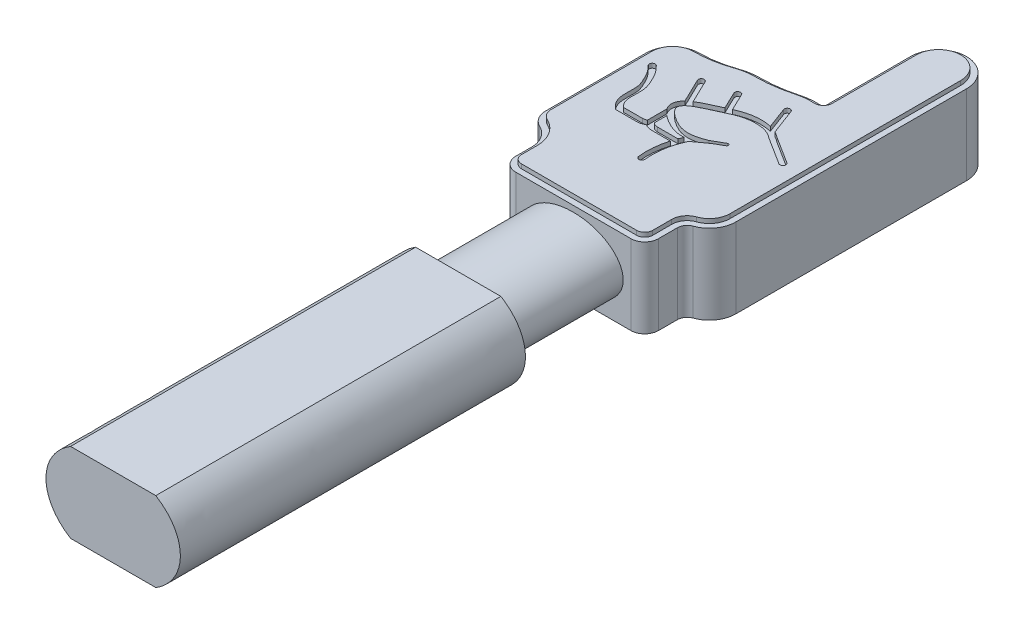
SolidWorks part; units mm, degrees
ref_plane "Plan de face" through (0, 0, 0) normal (0, 0, 1) x (1, 0, 0)
ref_plane "Plan de dessus" through (0, 0, 0) normal (0, 1, 0) x (1, 0, 0)
ref_plane "Plan de droite" through (0, 0, 0) normal (1, 0, 0) x (0, 0, -1)
sketch "Esquisse2" plane through (0, 0, 0) normal (0, 1, 0) x (1, 0, 0)
  line L4 (-461.3514, 50.6784) -> (-461.3514, 90.7755)
  line L5 (-471.0713, 90.7755) -> (-471.0713, 76.1755)
  line L6 (-465.5648, 44.7364) -> (-465.5648, 41.4326)
  line L7 (-467.9625, 39.035) -> (-487.9825, 39.035)
  line L8 (-490.3801, 41.4326) -> (-490.3801, 44.1985)
  line L9 (-494.5966, 50.8393) -> (-494.5966, 68.3008)
  arc A17 (-461.3514, 90.7755) -> (-471.0713, 90.7755) centre (-466.2114, 90.7755) ccw
  arc A18 (-471.0713, 76.1755) -> (-471.6659, 75.6215) centre (-471.6268, 76.1755) cw
  arc A19 (-471.6659, 75.6215) -> (-474.8438, 75.3021) centre (-472.3289, 66.2484) ccw
  arc A20 (-461.3514, 50.6784) -> (-464.4333, 46.3321) centre (-465.9571, 50.6784) cw
  arc A21 (-464.4333, 46.3321) -> (-465.5648, 44.7364) centre (-463.8739, 44.7364) ccw
  arc A22 (-465.5648, 41.4326) -> (-467.9625, 39.035) centre (-467.9625, 41.4326) cw
  arc A23 (-487.9825, 39.035) -> (-490.3801, 41.4326) centre (-487.9825, 41.4326) cw
  arc A24 (-490.3801, 44.1985) -> (-492.803, 48.0144) centre (-494.5966, 44.1985) ccw
  arc A25 (-492.803, 48.0144) -> (-494.5966, 50.8393) centre (-491.4751, 50.8393) cw
  arc A26 (-494.5966, 68.3008) -> (-489.9856, 72.9117) centre (-489.9856, 68.3008) cw
  arc A27 (-489.9856, 72.9117) -> (-484.1893, 73.9115) centre (-489.9856, 90.214) ccw
  arc A28 (-484.1893, 73.9115) -> (-480.9635, 74.4679) centre (-480.9635, 64.8387) cw
  arc A29 (-480.9635, 74.4679) -> (-474.8438, 75.3021) centre (-480.9635, 97.3326) ccw
  dimension "D3" = 14.6
  dimension "D4" = 0.5554
  dimension "D5" = 9.3965
  dimension "D6" = 4.6057
  dimension "D7" = 1.6909
  dimension "D8" = 2.3977
  dimension "D9" = 4.2164
  dimension "D10" = 3.1214
  dimension "D11" = 4.6109
  dimension "D12" = 17.3023
  dimension "D13" = 9.6292
  dimension "D1" = 9.72
  dimension "D2" = 461.3514
  dimension "D15" = 472.3289
  dimension "D16" = 465.5648
  dimension "D17" = 480.9635
  dimension "D18" = 484.1893
  dimension "D19" = 72.9117
  dimension "D21" = 50.8393
  dimension "D22" = 50.6784
  dimension "D36" = 39.035
extrude "Boss.-Extru.1" add sketch "Esquisse2" along normal blind 14.6
sketch "Esquisse4" plane through (0, 14.6, 0) normal (0, 1, 0) x (1, 0, 0)
  line L0 (-472.4313, 71.3413) -> (-470.759, 66.8763)
  line L1 (-479.2673, 69.577) -> (-477.8287, 66.5691)
  line L2 (-484.8272, 68.1421) -> (-483.1754, 64.6884)
  line L3 (-487.6052, 57.4055) -> (-484.2817, 57.4055)
  line L5 (-478.1514, 57.4055) -> (-481.7388, 57.4055)
  line L6 (-490.4583, 65.8897) -> (-491.0481, 66.5366)
  line L7 (-491.0481, 66.5366) -> (-472.4313, 71.3413) construction
  line L8 (-461.3514, 50.6784) -> (-461.3514, 90.7755) construction
  line L9 (-473.3677, 70.9906) -> (-471.9932, 67.3203)
  line L10 (-480.1694, 69.1456) -> (-478.7397, 66.1562)
  line L12 (-491.1972, 65.2159) -> (-491.787, 65.8628)
  line L13 (-487.9601, 56.4055) -> (-484.2783, 56.4055)
  line L14 (-477.4426, 56.4055) -> (-481.7388, 56.4055)
  line L16 (-483.1205, 57.4055) -> (-483.1205, 61.028) construction
  line L17 (-483.6205, 57.5979) -> (-483.6205, 60.9564)
  line L18 (-484.8272, 68.1421) -> (-482.7323, 63.7919) construction
  line L19 (-484.3767, 68.359) -> (-482.4341, 64.3251)
  line L20 (-485.2777, 67.9251) -> (-483.2443, 63.7026)
  line L21 (-470.3753, 65.4409) -> (-465.3514, 62.8537) construction
  line L22 (-469.8136, 66.2662) -> (-465.0842, 63.2763)
  line L23 (-470.348, 65.421) -> (-465.6185, 62.4311)
  line L24 (-473.0349, 60.7918) -> (-475.4776, 59.3877) construction
  line L25 (-472.8992, 60.5556) -> (-474.5084, 59.6306)
  line L26 (-473.1707, 61.028) -> (-475.2006, 59.8612)
  line L27 (-482.6205, 57.7552) -> (-482.6205, 59.9234)
  arc A0 (-484.2817, 57.4055) -> (-483.6205, 57.5979) centre (-484.2916, 58.6719) ccw
  arc A1 (-476.8297, 57.9491) -> (-477.9359, 51.4698) centre (-466.0442, 52.7736) ccw
  arc A3 (-481.7388, 57.4055) -> (-482.6205, 57.7552) centre (-481.7388, 58.692) cw
  arc A5 (-484.2783, 56.4055) -> (-483.0183, 56.797) centre (-484.2916, 58.6719) ccw
  arc A6 (-481.7388, 56.4055) -> (-483.0183, 56.797) centre (-481.7388, 58.692) cw
  arc A7 (-477.8343, 58.1619) -> (-478.1514, 57.4055) centre (-466.0442, 52.7736) ccw
  arc A8 (-472.4313, 71.3413) -> (-473.3677, 70.9906) centre (-472.8995, 71.1659) ccw
  arc A10 (-479.2673, 69.577) -> (-480.1694, 69.1456) centre (-479.7183, 69.3613) ccw
  arc A14 (-491.0481, 66.5366) -> (-491.787, 65.8628) centre (-491.4176, 66.1997) ccw
  arc A18 (-470.4025, 65.4609) -> (-470.348, 65.421) centre (-470.3753, 65.4409) ccw
  arc A19 (-477.9359, 51.4698) -> (-478.93, 51.3609) centre (-478.433, 51.4154) cw
  arc A21 (-484.3767, 68.359) -> (-485.2777, 67.9251) centre (-484.8272, 68.1421) ccw
  arc A23 (-470.4025, 65.4609) -> (-470.348, 65.421) centre (-470.3753, 65.4409) ccw
  arc A24 (-465.6185, 62.4311) -> (-465.0842, 63.2763) centre (-465.3514, 62.8537) ccw
  arc A25 (-472.8992, 60.5556) -> (-473.1707, 61.028) centre (-473.0349, 60.7918) ccw
  arc A27 (-478.488, 56.4055) -> (-478.93, 51.3609) centre (-466.0442, 52.7736) ccw
  spline S0 degree 3 poles (-490.4583, 65.8897) (-489.9643, 65.3478) (-489.2576, 64.0084) (-488.0431, 61.1753) (-489.0579, 58.5852) (-487.6052, 57.4055) knots 0 0 0 0 0.249547 0.474449 1 1 1 1
  spline S1 degree 3 poles (-483.1823, 64.7264) (-483.18, 64.7137) (-483.1777, 64.7011) (-483.1754, 64.6884) knots 0.246141 0.246141 0.246141 0.246141 0.248714 0.248714 0.248714 0.248714
  spline S2 degree 3 poles (-470.4025, 65.4609) (-471.657, 66.5152) (-475.3225, 66.8063) (-478.8719, 64.9069) (-484.364, 62.5575) (-480.7126, 59.6038) (-478.2259, 58.8088) (-475.901, 59.5831) (-475.2006, 59.8612) knots 0 0 0 0 0.163612 0.32751 0.477242 0.563601 0.697734 0.765481 0.765481 0.765481 0.765481
  spline S3 degree 2 poles (-474.5084, 59.6306) (-475.3996, 58.9745) (-476.8297, 57.9491) knots 0.955294 0.955294 0.955294 1 1 1
  spline S4 degree 3 poles (-483.2443, 63.7026) (-483.4189, 63.536) (-483.7603, 63.1422) (-484.042, 62.4144) (-483.9809, 61.7052) (-483.8197, 61.2849) (-483.6856, 61.0541) (-483.6205, 60.9564) knots 0.428302 0.428302 0.428302 0.428302 0.447364 0.468667 0.479319 0.48997 0.498689 0.498689 0.498689 0.498689
  spline S5 degree 3 poles (-478.7397, 66.1562) (-478.841, 66.109) (-479.3545, 65.8687) (-480.3361, 65.4112) (-481.5724, 64.8367) (-482.2436, 64.4471) (-482.4341, 64.3251) knots 0.287644 0.287644 0.287644 0.287644 0.298243 0.340849 0.383455 0.401257 0.401257 0.401257 0.401257
  spline S6 degree 3 poles (-491.1972, 65.2159) (-491.0951, 65.1039) (-490.914, 64.8749) (-490.5473, 64.3017) (-490.1129, 63.4322) (-489.672, 62.4162) (-489.5049, 61.5865) (-489.5458, 60.4567) (-489.5779, 59.3459) (-489.4093, 58.37) (-489.1649, 57.7435) (-488.8551, 57.2619) (-488.58, 56.9296) (-488.2037, 56.5974) (-488.0493, 56.478) (-487.9601, 56.4055) knots 0 0 0 0 0.064576 0.129153 0.258306 0.387458 0.516611 0.645764 0.774917 0.839493 0.90407 0.936358 0.968646 1.000934 1.033223 1.033223 1.033223 1.033223
  spline S7 degree 3 poles (-471.9932, 67.3203) (-472.1805, 67.365) (-473.344, 67.5872) (-475.4797, 67.4725) (-477.0435, 66.9088) (-477.8287, 66.5691) knots 0.068798 0.068798 0.068798 0.068798 0.085212 0.170424 0.255222 0.255222 0.255222 0.255222
  spline S8 degree 3 poles (-469.7591, 66.2264) (-470.0622, 66.4812) (-470.4037, 66.6993) (-470.759, 66.8763) knots 0 0 0 0 0.03228 0.03228 0.03228 0.03228
  spline S9 degree 3 poles (-482.6205, 59.9234) (-482.4376, 59.7779) (-481.8068, 59.3219) (-480.7516, 58.706) (-479.3663, 58.2092) (-478.3366, 58.1325) (-477.8343, 58.1619) knots 0.535686 0.535686 0.535686 0.535686 0.553879 0.596485 0.639091 0.681698 0.681698 0.681698 0.681698
  point P38 (-483.7797, 65.967)
  point P58 (-483.1205, 59.2167)
  point P61 (-474.2563, 60.0898)
  point P67 (-467.7161, 64.3487)
  dimension "D4" = 1.2865
  dimension "D6" = 4.6928
  dimension "D9" = 2.2865
  dimension "D10" = 11.0799
  dimension "D11" = 11.1625
  dimension "D13" = 13.661
  dimension "D1" = 1.2664
  dimension "D2" = 11.963
  dimension "D5" = 0.5
  dimension "D7" = 2.2664
  dimension "D12" = 0.0338
  dimension "D15" = 0.2724
  dimension "D8" = 1
  dimension "D14" = 15.4783
  dimension "D16" = 16.0443
  dimension "D17" = 3.7328
  dimension "D18" = 16.5846
  dimension "D19" = 17.9159
  dimension "D20" = 18.1649
  dimension "D21" = 1
  dimension "D22" = 20.3874
  dimension "D23" = 21.6423
  dimension "D24" = 4
  dimension "D25" = 21.824
  dimension "D26" = 5.1377
  dimension "D27" = 4.2671
  dimension "D28" = 23.4758
  dimension "D29" = 26.2538
  dimension "D30" = 27.0797
  dimension "D31" = 27.2299
  dimension "D32" = 27.9056
  dimension "D33" = 29.1069
  dimension "D34" = 29.6967
  dimension "D35" = 12.8812
  dimension "D36" = 13.8294
  dimension "D37" = 6.3647
  dimension "D38" = 8.4077
  dimension "D39" = 17.6054
  dimension "D40" = 18.3562
  dimension "D41" = 8.4623
  dimension "D42" = 9.0239
  dimension "D43" = 19.5575
  dimension "D44" = 11.5481
  dimension "D45" = 16.0912
  dimension "D46" = 9.4077
  dimension "D47" = 10.6418
  dimension "D48" = 11.5478
  dimension "D49" = 18.3669
  dimension "D50" = 11.6836
  dimension "D51" = 11.8193
  dimension "D52" = 21.2691
  dimension "D53" = 12.9049
  dimension "D54" = 13.157
  dimension "D55" = 13.8492
  dimension "D56" = 21.6669
  dimension "D57" = 16.4773
  dimension "D58" = 16.4829
  dimension "D59" = 23.0253
  dimension "D60" = 30.0662
  dimension "D61" = 12.8846
  dimension "D62" = 17.3883
  dimension "D63" = 16.099
  dimension "D64" = 12.3497
  dimension "D65" = 18.3943
  dimension "D66" = 19.8742
  dimension "D67" = 21.0827
  dimension "D70" = 21.7691
  dimension "D71" = 21.8309
  dimension "D72" = 21.8929
  dimension "D73" = 13.5913
  dimension "D74" = 22.4283
  dimension "D75" = 13.7576
  dimension "D79" = 15.6533
  dimension "D80" = 26.6087
  dimension "D84" = 18.0165
  dimension "D90" = 19.8943
  dimension "D92" = 20.076
extrude "Cut-Extrude1" cut sketch "Esquisse4" against normal blind 0.75 contours S8 L0 A8 L9 S7 L1 A10 L10 S5 L19 A21 L20 S4 L17 A0 L3 S0 L6 A14 L12 S6 L13 A5 A6 L14 A1 S3 L25 A25 L26 S2 A18 L23 A24 L22 L27 S9 A7 L5 A3 | L14 A27 A19 A1 region at (-471.8861, 14.6, -68.9998) region at (-478.3729, 14.6, -53.7296)
sketch "Sketch1" plane through (0, 14.6, 0) normal (0, 1, 0) x (1, 0, 0)
  line L0 (-462.3514, 50.6784) -> (-462.3514, 90.7755)
  line L1 (-470.0713, 90.7755) -> (-470.0713, 76.1755)
  line L2 (-493.5966, 68.3008) -> (-493.5966, 50.8393)
  line L3 (-489.3801, 44.1985) -> (-489.3801, 41.4326)
  line L4 (-487.9825, 40.035) -> (-467.9625, 40.035)
  line L5 (-466.5648, 41.4326) -> (-466.5648, 44.7364)
  line L6 (-461.3514, 50.6784) -> (-461.3514, 90.7755)
  line L7 (-471.0713, 90.7755) -> (-471.0713, 76.1755)
  line L8 (-494.5966, 68.3008) -> (-494.5966, 50.8393)
  line L9 (-490.3801, 44.1985) -> (-490.3801, 41.4326)
  line L10 (-487.9825, 39.035) -> (-467.9625, 39.035)
  line L11 (-465.5648, 41.4326) -> (-465.5648, 44.7364)
  line L12 (-461.3514, 50.6784) -> (-461.3514, 90.7755)
  line L13 (-471.0713, 90.7755) -> (-471.0713, 76.1755)
  line L14 (-494.5966, 68.3008) -> (-494.5966, 50.8393)
  line L15 (-490.3801, 44.1985) -> (-490.3801, 41.4326)
  line L16 (-487.9825, 39.035) -> (-467.9625, 39.035)
  line L17 (-465.5648, 41.4326) -> (-465.5648, 44.7364)
  arc A0 (-464.7642, 47.2758) -> (-462.3514, 50.6784) centre (-465.9571, 50.6784) ccw
  arc A1 (-462.3514, 90.7755) -> (-470.0713, 90.7755) centre (-466.2114, 90.7755) ccw
  arc A2 (-471.7365, 74.624) -> (-470.0713, 76.1755) centre (-471.6268, 76.1755) ccw
  arc A3 (-471.7365, 74.624) -> (-474.5762, 74.3386) centre (-472.3289, 66.2484) ccw
  arc A4 (-480.9635, 73.4679) -> (-474.5762, 74.3386) centre (-480.9635, 97.3326) ccw
  arc A5 (-480.9635, 73.4679) -> (-483.8543, 72.9693) centre (-480.9635, 64.8387) ccw
  arc A6 (-489.9856, 71.9117) -> (-483.8543, 72.9693) centre (-489.9856, 90.214) ccw
  arc A7 (-489.9856, 71.9117) -> (-493.5966, 68.3008) centre (-489.9856, 68.3008) ccw
  arc A8 (-493.5966, 50.8393) -> (-492.3776, 48.9194) centre (-491.4751, 50.8393) ccw
  arc A9 (-489.3801, 44.1985) -> (-492.3776, 48.9194) centre (-494.5966, 44.1985) ccw
  arc A10 (-489.3801, 41.4326) -> (-487.9825, 40.035) centre (-487.9825, 41.4326) ccw
  arc A11 (-467.9625, 40.035) -> (-466.5648, 41.4326) centre (-467.9625, 41.4326) ccw
  arc A12 (-464.7642, 47.2758) -> (-466.5648, 44.7364) centre (-463.8739, 44.7364) ccw
  arc A13 (-464.4333, 46.3321) -> (-461.3514, 50.6784) centre (-465.9571, 50.6784) ccw
  arc A14 (-461.3514, 90.7755) -> (-471.0713, 90.7755) centre (-466.2114, 90.7755) ccw
  arc A15 (-471.6659, 75.6215) -> (-471.0713, 76.1755) centre (-471.6268, 76.1755) ccw
  arc A16 (-471.6659, 75.6215) -> (-474.8438, 75.3021) centre (-472.3289, 66.2484) ccw
  arc A17 (-480.9635, 74.4679) -> (-474.8438, 75.3021) centre (-480.9635, 97.3326) ccw
  arc A18 (-480.9635, 74.4679) -> (-484.1893, 73.9115) centre (-480.9635, 64.8387) ccw
  arc A19 (-489.9856, 72.9117) -> (-484.1893, 73.9115) centre (-489.9856, 90.214) ccw
  arc A20 (-489.9856, 72.9117) -> (-494.5966, 68.3008) centre (-489.9856, 68.3008) ccw
  arc A21 (-494.5966, 50.8393) -> (-492.803, 48.0144) centre (-491.4751, 50.8393) ccw
  arc A22 (-490.3801, 44.1985) -> (-492.803, 48.0144) centre (-494.5966, 44.1985) ccw
  arc A23 (-490.3801, 41.4326) -> (-487.9825, 39.035) centre (-487.9825, 41.4326) ccw
  arc A24 (-467.9625, 39.035) -> (-465.5648, 41.4326) centre (-467.9625, 41.4326) ccw
  arc A25 (-464.4333, 46.3321) -> (-465.5648, 44.7364) centre (-463.8739, 44.7364) ccw
  arc A26 (-464.4333, 46.3321) -> (-461.3514, 50.6784) centre (-465.9571, 50.6784) ccw
  arc A27 (-461.3514, 90.7755) -> (-471.0713, 90.7755) centre (-466.2114, 90.7755) ccw
  arc A28 (-471.6659, 75.6215) -> (-471.0713, 76.1755) centre (-471.6268, 76.1755) ccw
  arc A29 (-471.6659, 75.6215) -> (-474.8438, 75.3021) centre (-472.3289, 66.2484) ccw
  arc A30 (-480.9635, 74.4679) -> (-474.8438, 75.3021) centre (-480.9635, 97.3326) ccw
  arc A31 (-480.9635, 74.4679) -> (-484.1893, 73.9115) centre (-480.9635, 64.8387) ccw
  arc A32 (-489.9856, 72.9117) -> (-484.1893, 73.9115) centre (-489.9856, 90.214) ccw
  arc A33 (-489.9856, 72.9117) -> (-494.5966, 68.3008) centre (-489.9856, 68.3008) ccw
  arc A34 (-494.5966, 50.8393) -> (-492.803, 48.0144) centre (-491.4751, 50.8393) ccw
  arc A35 (-490.3801, 44.1985) -> (-492.803, 48.0144) centre (-494.5966, 44.1985) ccw
  arc A36 (-490.3801, 41.4326) -> (-487.9825, 39.035) centre (-487.9825, 41.4326) ccw
  arc A37 (-467.9625, 39.035) -> (-465.5648, 41.4326) centre (-467.9625, 41.4326) ccw
  arc A38 (-464.4333, 46.3321) -> (-465.5648, 44.7364) centre (-463.8739, 44.7364) ccw
  dimension "D1" = 0
  dimension "D2" = 1
extrude "Cut-Extrude2" cut sketch "Sketch1" against normal blind 0.75
sketch "Sketch3" plane through (0, 0, -39.035) normal (0, 0, 1) x (1, 0, 0)
  line L0 (-487.9825, 13.85) -> (-467.9625, 13.85) construction
  line L1 (-487.9825, 13.85) -> (-487.9825, 0) construction
  ellipse E0 centre (-477.9825, 6.925) end of major axis (-486.6636, 6.925) minor radius 5.9038
  point P1 (-469.6345, 7.2248)
  point P7 (-478.3155, 1.321)
  point P8 (0, 0)
  dimension "D1" = 6.925
  dimension "D2" = 10
extrude "Boss-Extrude1" add sketch "Sketch3" along normal blind 20
sketch "Sketch4" plane through (0, 0, -19.035) normal (0, 0, 1) x (1, 0, 0)
  line L0 (-470.5731, 13.85) -> (-485.3919, 13.85)
  line L1 (-487.9825, 13.85) -> (-467.9625, 13.85) construction
  line L2 (-485.3918, 0) -> (-470.5732, 0)
  line L3 (-487.9825, 0) -> (-467.9625, 0) construction
  spline S0 degree 3 poles (-466.3014, 6.2388) (-466.3014, 7.6112) (-466.4006, 8.28) (-466.6889, 9.2587) (-466.8094, 9.5817) (-467.0888, 10.201) (-467.2484, 10.4997) (-467.6048, 11.0766) (-467.8026, 11.356) (-468.2294, 11.8893) (-468.4569, 12.1415) (-468.9373, 12.6198) (-469.1902, 12.846) (-469.7198, 13.2739) (-469.9971, 13.4759) (-470.8466, 14.0371) (-471.4407, 14.3559) (-472.3673, 14.7636) (-472.6822, 14.8877) (-473.3233, 15.113) (-473.65, 15.2142) (-474.6313, 15.4807) (-475.2921, 15.6109) (-476.6258, 15.7849) (-477.2986, 15.8286) (-478.317, 15.829) (-478.6584, 15.818) (-479.3346, 15.7743) (-479.6706, 15.7416) (-480.6722, 15.6111) (-481.3315, 15.481) (-482.3069, 15.2166) (-482.6297, 15.1168) (-483.2705, 14.8923) (-483.5893, 14.7671) (-484.5216, 14.3575) (-485.1164, 14.0381) (-485.9627, 13.4795) (-486.2372, 13.28) (-486.7688, 12.8511) (-487.0234, 12.6237) (-487.7438, 11.9073) (-488.1702, 11.3821) (-488.8926, 10.2167) (-489.1723, 9.6026) (-489.4615, 8.6331) (-489.5362, 8.3008) (-489.6372, 7.6223) (-489.6626, 7.2836) (-489.6645, 6.6075) (-489.6412, 6.2701) (-489.5453, 5.5963) (-489.4719, 5.2587) (-489.2811, 4.6058) (-489.1634, 4.2879) (-488.8858, 3.6682) (-488.7247, 3.3646) (-488.1874, 2.4915) (-487.7619, 1.9628) (-487.0368, 1.2385) (-486.7814, 1.0099) (-486.2544, 0.5831) (-485.9815, 0.3838) (-485.4187, 0.0106) (-485.1287, -0.1632) (-484.5328, -0.4868) (-484.2256, -0.6371) (-483.2899, -1.0495) (-482.6521, -1.272) (-481.3522, -1.6264) (-480.6901, -1.7582) (-479.6795, -1.8907) (-479.3391, -1.924) (-478.6616, -1.9679) (-478.3234, -1.9788) (-477.3105, -1.979) (-476.6375, -1.9361) (-475.296, -1.7618) (-474.623, -1.6288) (-473.3156, -1.273) (-472.6788, -1.0506) (-471.7518, -0.6429) (-471.4475, -0.4946) (-470.8493, -0.1708) (-470.5547, 0.0053) (-469.7047, 0.5681) (-469.1773, 0.9911) (-468.4555, 1.71) (-468.2252, 1.9656) (-467.7996, 2.4981) (-467.6038, 2.7749) (-467.2482, 3.3508) (-467.0883, 3.6499) (-466.8077, 4.2722) (-466.6877, 4.5951) (-466.4009, 5.5698) (-466.3014, 6.2388) (-466.3014, 7.6112) (-466.4006, 8.28) knots -0.03125 -0.03125 0 0 0.03125 0.03125 0.046875 0.046875 0.0625 0.0625 0.078125 0.078125 0.09375 0.09375 0.109375 0.109375 0.125 0.125 0.15625 0.15625 0.171875 0.171875 0.1875 0.1875 0.21875 0.21875 0.25 0.25 0.265625 0.265625 0.28125 0.28125 0.3125 0.3125 0.328125 0.328125 0.34375 0.34375 0.375 0.375 0.390625 0.390625 0.40625 0.40625 0.4375 0.4375 0.46875 0.46875 0.484375 0.484375 0.5 0.5 0.515625 0.515625 0.53125 0.53125 0.546875 0.546875 0.5625 0.5625 0.59375 0.59375 0.609375 0.609375 0.625 0.625 0.640625 0.640625 0.65625 0.65625 0.6875 0.6875 0.71875 0.71875 0.734375 0.734375 0.75 0.75 0.78125 0.78125 0.8125 0.8125 0.84375 0.84375 0.859375 0.859375 0.875 0.875 0.90625 0.90625 0.921875 0.921875 0.9375 0.9375 0.953125 0.953125 0.96875 0.96875 1 1 1.03125 1.03125 1.046875 only from (-466.3014, 6.925) to (-466.3014, 6.925)
  spline S1 degree 3 poles (-485.3919, 13.85) (-485.489, 13.7901) (-485.5852, 13.7286) (-485.9627, 13.4795) (-486.2372, 13.28) (-486.7688, 12.8511) (-487.0234, 12.6237) (-487.7438, 11.9073) (-488.1702, 11.3821) (-488.8926, 10.2167) (-489.1723, 9.6026) (-489.4615, 8.6331) (-489.5362, 8.3008) (-489.6372, 7.6223) (-489.6879, 6.945) (-489.6412, 6.2701) (-489.5453, 5.5963) (-489.4719, 5.2587) (-489.2811, 4.6058) (-489.1634, 4.2879) (-488.8858, 3.6682) (-488.7247, 3.3646) (-488.1874, 2.4915) (-487.7619, 1.9628) (-487.0368, 1.2385) (-486.7814, 1.0099) (-486.2544, 0.5831) (-485.883, 0.3118) (-485.4957, 0.0641) (-485.3918, 0) knots 0.369718 0.369718 0.369718 0.369718 0.375 0.375 0.390625 0.390625 0.40625 0.40625 0.4375 0.4375 0.46875 0.46875 0.484375 0.484375 0.5 0.515625 0.515625 0.53125 0.53125 0.546875 0.546875 0.5625 0.5625 0.59375 0.59375 0.609375 0.609375 0.625 0.630644 0.630644 0.630644 0.630644
  spline S2 degree 3 poles (-470.5732, 0) (-470.4714, 0.0628) (-470.3707, 0.1272) (-469.7047, 0.5681) (-469.1773, 0.9911) (-468.4555, 1.71) (-468.2252, 1.9656) (-467.7996, 2.4981) (-467.6038, 2.7749) (-467.2482, 3.3508) (-467.0883, 3.6499) (-466.8077, 4.2722) (-466.6877, 4.5951) (-466.4009, 5.5698) (-466.3014, 6.2388) (-466.3014, 7.6112) (-466.4006, 8.28) (-466.6889, 9.2587) (-466.8094, 9.5817) (-467.0888, 10.201) (-467.2484, 10.4997) (-467.6048, 11.0766) (-467.8026, 11.356) (-468.2294, 11.8893) (-468.4569, 12.1415) (-468.9373, 12.6198) (-469.1902, 12.846) (-469.7198, 13.2739) (-469.9971, 13.4759) (-470.3771, 13.7269) (-470.4747, 13.7893) (-470.5731, 13.85) knots 0.869523 0.869523 0.869523 0.869523 0.875 0.875 0.90625 0.90625 0.921875 0.921875 0.9375 0.9375 0.953125 0.953125 0.96875 0.96875 1 1 1.03125 1.03125 1.046875 1.046875 1.0625 1.0625 1.078125 1.078125 1.09375 1.09375 1.109375 1.109375 1.125 1.125 1.130341 1.130341 1.130341 1.130341
  dimension "D1" = 3
extrude "Boss-Extrude4" add sketch "Sketch4" along normal blind 60
